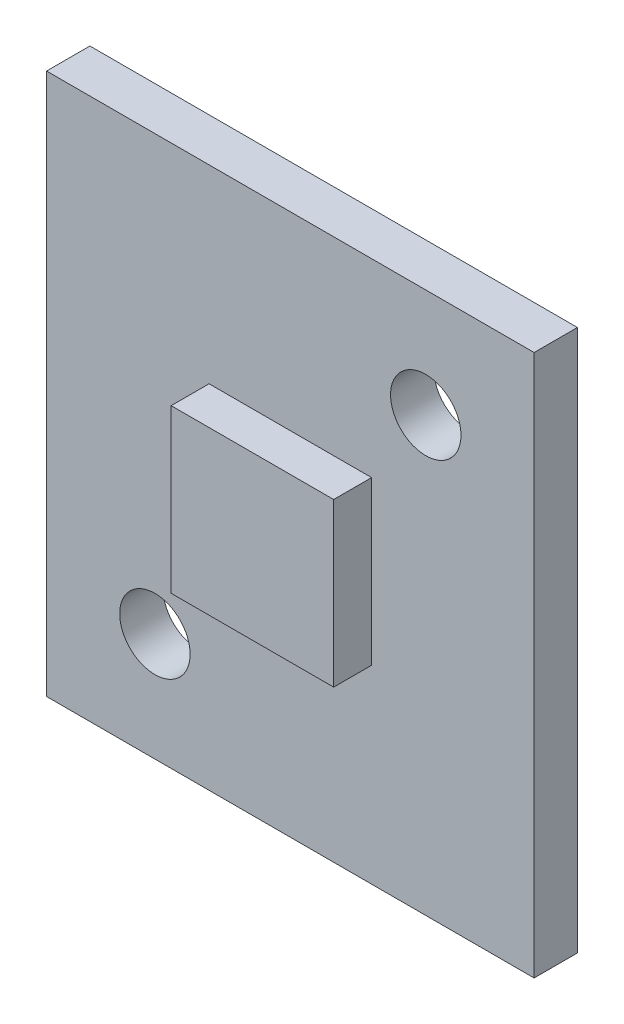
SolidWorks part; units mm, degrees
ref_plane "前视基准面" through (0, 0, 0) normal (0, 0, 1) x (1, 0, 0)
ref_plane "上视基准面" through (0, 0, 0) normal (0, 1, 0) x (1, 0, 0)
ref_plane "右视基准面" through (0, 0, 0) normal (1, 0, 0) x (0, 0, -1)
other "Configuration Table"
sketch "草图1" plane through (0, 0, 0) normal (0, 0, 1) x (1, 0, 0)
  line L1 (-72, -70) -> (-54, -70)
  line L2 (-72, -70) -> (-72, -50)
  line L3 (-72, -50) -> (-54, -50)
  line L4 (-54, -70) -> (-54, -50)
extrude "Rigid_IMU_reference" [suppressed] add sketch "草图1" along normal blind 3 from offset 38
sketch "草图2" plane through (0, 0, 0) normal (0, 0, 1) x (1, 0, 0)
  line L1 (-74, -70) -> (-56, -70)
  line L2 (-74, -70) -> (-74, -50)
  line L3 (-74, -50) -> (-56, -50)
  line L4 (-56, -70) -> (-56, -50)
extrude "V10_IMU_candidate18x20" add sketch "草图2" along normal blind 1.6 from offset 38
sketch "草图3" plane through (0, 0, 0) normal (0, 0, 1) x (1, 0, 0)
  line L1 (-68, -63) -> (-62, -63)
  line L2 (-68, -63) -> (-68, -57)
  line L3 (-68, -57) -> (-62, -57)
  line L4 (-62, -63) -> (-62, -57)
extrude "V10_IMU_package" add sketch "草图3" along normal blind 1.4 from offset 39.6
sketch "草图4" plane through (0, 0, 39.6) normal (0, 0, 1) x (1, 0, 0)
  circle A0 centre (-70, -66) radius 1.3
  circle A1 centre (-60, -54) radius 1.3
extrude "V10_IMU_diagonal_candidate_holes" cut sketch "草图4" against normal blind 1.6
